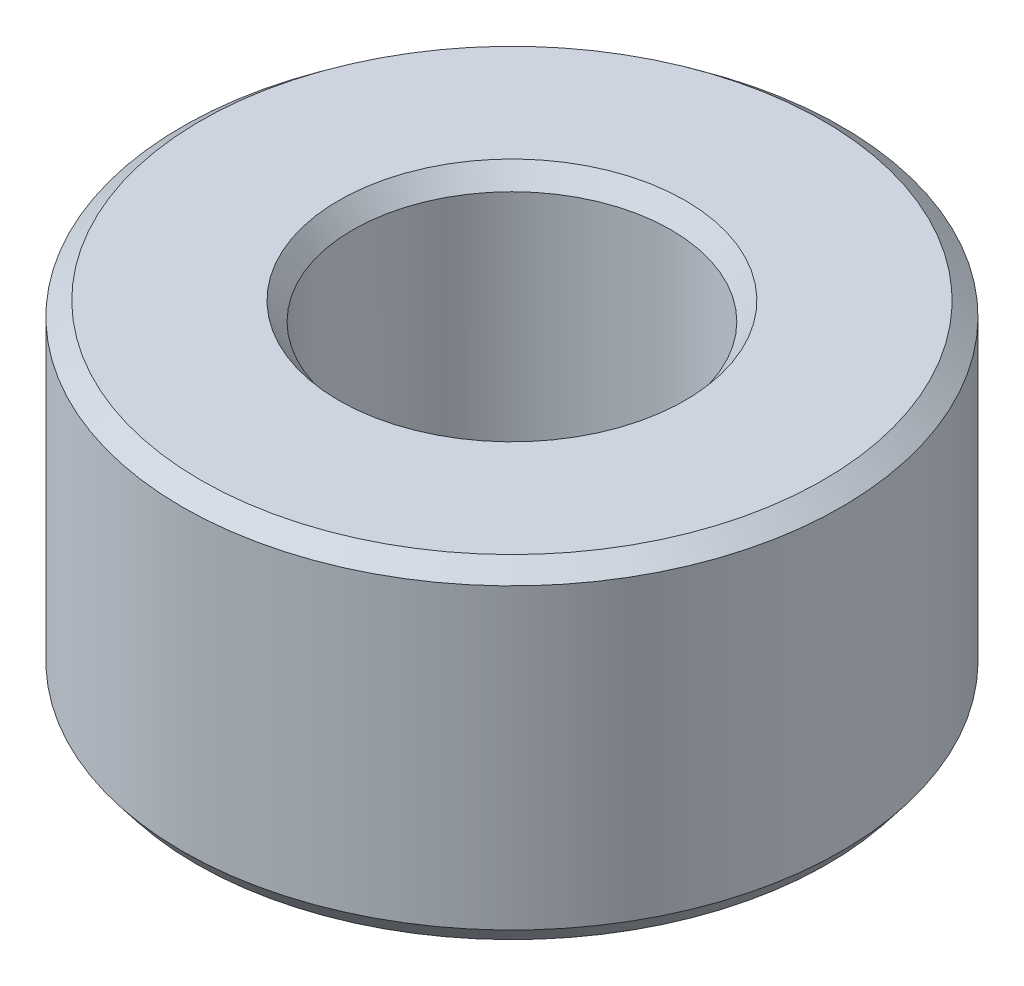
SolidWorks part; units mm, degrees
ref_plane "Front Plane" through (0, 0, 0) normal (0, 0, 1) x (1, 0, 0)
ref_plane "Top Plane" through (0, 0, 0) normal (0, 1, 0) x (1, 0, 0)
ref_plane "Right Plane" through (0, 0, 0) normal (1, 0, 0) x (0, 0, -1)
sketch "Sketch1" plane through (0, 0, 0) normal (0, 1, 0) x (1, 0, 0)
  circle A0 centre (0, 0) radius 52.5
  dimension "SLEEVE_OD" = 105
extrude "Boss-Extrude1" add sketch "Sketch1" along normal blind 52.6571
sketch "Sketch2" plane through (0, 0, 0) normal (0, 1, 0) x (1, 0, 0)
  circle A0 centre (0, 0) radius 25.335
  dimension "BORE_D" = 50.67
extrude "Cut-Extrude1" cut sketch "Sketch2" along normal through all
chamfer "Chamfer1" distance 2.2589 angle 52.249 4 edges at (0, 52.6571, 25.335) (0, 0, 25.335) (0, 0, 52.5) (0, 52.6571, 52.5) first distance on face at (0, 52.6571, 25.335) first distance on face at (0, 0, 25.335) first distance on face at (0, 52.6571, 52.5)
